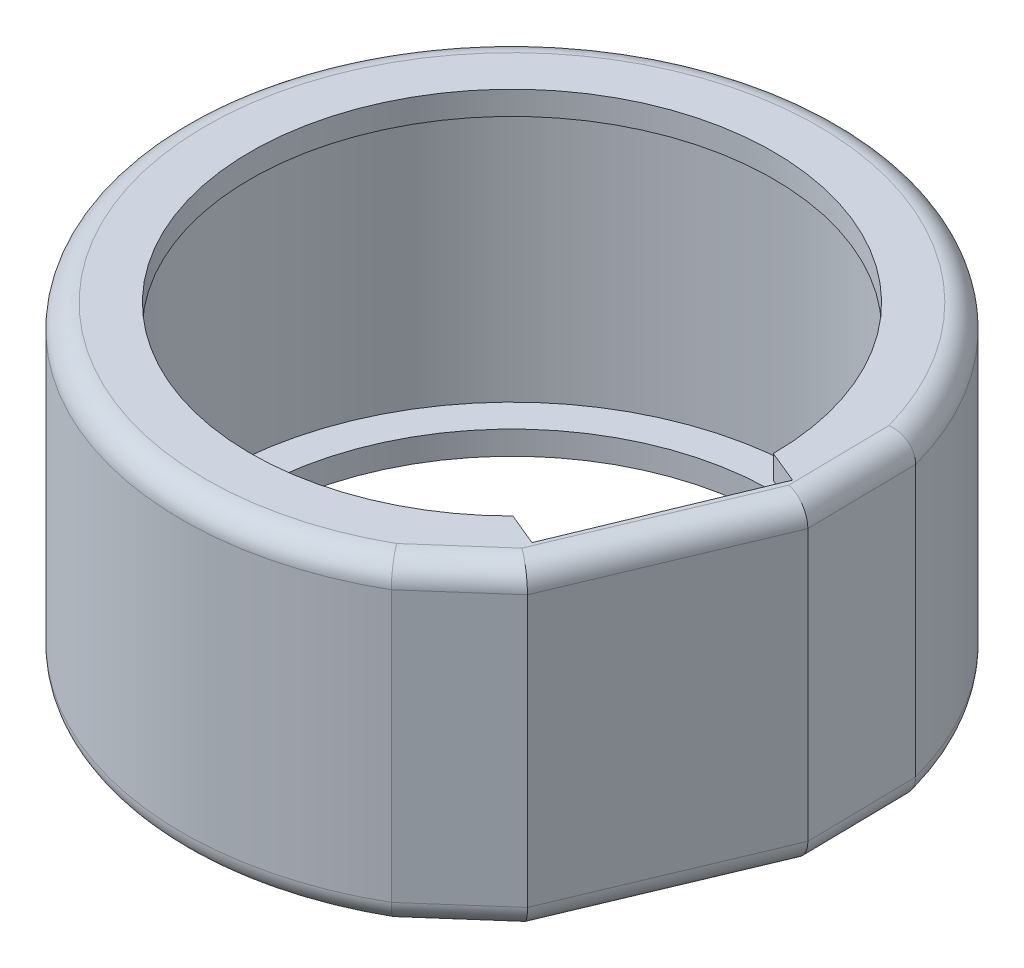
SolidWorks part; units mm, degrees
ref_plane "前视基准面" through (0, 0, 0) normal (0, 0, 1) x (1, 0, 0)
ref_plane "上视基准面" through (0, 0, 0) normal (0, 1, 0) x (1, 0, 0)
ref_plane "右视基准面" through (0, 0, 0) normal (1, 0, 0) x (0, 0, -1)
sketch "草图1" plane through (0, 0, 0) normal (0, 1, 0) x (1, 0, 0)
  line L0 (0, 0) -> (11.1, 0) construction
  line L1 (0, 0) -> (7.8676, -7.8301) construction
  line L6 (0, 0) -> (13.523, 3.6235) construction
  line L7 (0, 0) -> (7, -12.1244) construction
  line L10 (11.1, 0) -> (13.5957, -1.0303) construction
  line L20 (13.5957, -1.0303) -> (10.076, -9.4184)
  line L21 (13.5957, -1.0303) -> (13.523, 3.6235)
  line L22 (10.076, -9.4184) -> (7, -12.1244)
  line L23 (11.1, 0) -> (7.8676, -7.8301)
  arc A0 (11.1, 0) -> (7.8676, -7.8301) centre (0, 0) ccw
  arc A3 (13.523, 3.6235) -> (7, -12.1244) centre (0, 0) ccw
  dimension "D1" = 2.7
  dimension "D2" = 14
  dimension "D3" = 11.1
extrude "凸台-拉伸1" add sketch "草图1" along normal blind 1
sketch "草图2" plane through (0, 0, 0) normal (0, -1, 0) x (-1, 0, 0)
  line L5 (0, 0) -> (-7, -12.1244) construction
  line L7 (0, 0) -> (-13.523, 3.6235) construction
  line L9 (-9.2267, -8.4332) -> (-12.4874, -0.5611)
  line L17 (-13.5957, -1.0303) -> (-13.523, 3.6235)
  line L19 (-13.5957, -1.0303) -> (-10.076, -9.4184)
  line L20 (-10.076, -9.4184) -> (-7, -12.1244)
  arc A0 (-7, -12.1244) -> (-13.523, 3.6235) centre (0, 0) ccw
  arc A1 (-9.2267, -8.4332) -> (-12.4874, -0.5611) centre (0, 0) ccw
  dimension "D1" = 12.5
  dimension "D2" = 14
extrude "凸台-拉伸3" add sketch "草图2" along normal blind 11.5
sketch "草图5" plane through (0, -11.5, 0) normal (0, -1, 0) x (-1, 0, 0)
  line L4 (0, 0) -> (-7, -12.1244) construction
  line L5 (0, 0) -> (-13.523, 3.6235) construction
  line L17 (-13.523, 3.6235) -> (-13.5957, -1.0303)
  line L19 (-10.076, -9.4184) -> (-7, -12.1244)
  line L21 (-11.1, 0) -> (-7.8676, -7.8301) construction
  line L22 (-11.1, 0) -> (-7.8676, -7.8301)
  line L23 (-13.5957, -1.0303) -> (-10.076, -9.4184)
  arc A1 (-7, -12.1244) -> (-13.523, 3.6235) centre (0, 0) ccw
  arc A2 (-7.8676, -7.8301) -> (-11.1, 0) centre (0, 0) ccw construction
  arc A3 (-7.8676, -7.8301) -> (-11.1, 0) centre (0, 0) ccw
extrude "凸台-拉伸4" add sketch "草图5" along normal blind 1
fillet "圆角1" radius 1 4 edges at (13.5593, -12.5, -1.2966) (-12.9343, -12.5, -5.3576) (8.538, -12.5, 10.7714) (11.8358, -12.5, 5.2243) type face fillet first side face at (13.5593, -5.75, -1.2966) first side face at (11.8358, -5.75, 5.2243) first side face at (8.538, -5.75, 10.7714) first side face at (-1.3364, -5.75, -0.5536) second side face at (5.2497, -12.5, 2.3354)
fillet "圆角2" radius 1 4 edges at (13.5593, 1, -1.2966) (-12.9343, 1, -5.3576) (8.538, 1, 10.7714) (11.8358, 1, 5.2243) type face fillet first side face at (13.5593, -5.25, -1.2966) first side face at (11.8358, -5.25, 5.2243) first side face at (8.538, -5.25, 10.7714) first side face at (-1.3364, -5.25, -0.5536) second side face at (-0.3882, 1, -0.1602)
sketch "草图7" plane through (9.4838, 0, 3.9151) normal (-0.9243, 0, -0.3816) x (-0.3816, 0, 0.9243)
  line L4 (-4.2355, 1) -> (-4.2355, 0) construction
  line L5 (-4.2355, 1) -> (-4.2355, 0)
  line L6 (-4.2355, 1) -> (4.2355, 1) construction
  line L7 (-4.2355, 1) -> (4.2355, 1)
  line L9 (-4.2355, 0) -> (4.2355, 0)
  line L10 (-4.2355, 0) -> (-4.2355, 1)
  line L11 (-4.2355, 1) -> (4.2355, 1)
  line L12 (4.2355, 0) -> (4.2355, 1)
extrude "切除-拉伸1" cut sketch "草图7" against normal blind 1.5 contours L9 L12 L7 L5
sketch3d "3DSketch1"
  spline S0 degree 1 poles (-13.1347, 1999.9934, 4.8456) (-13.1347, -2011.4808, 4.8456) knots -173.912465 -173.912465 174.91137 174.91137 only from (-13.1347, 0, 4.8456) to (-13.1347, -11.5, 4.8456) construction
  spline S1 degree 1 poles (-13.1347, 0, 4.8456) (-13.1347, -11.5, 4.8456) knots 0 0 1 1
sketch3d "3DSketch2"
  spline S0 degree 3 poles (7, -5.75, 12.1244) (-6.9766, -5.75, 20.1937) (-19.1104, -5.75, 9.5527) (-12.9343, -5.75, -5.3576) (-6.7583, -5.75, -20.2678) (9.3459, -5.75, -19.2123) (13.523, -5.75, -3.6235) knots 0 0 0 0 0.5 0.5 0.5 1 1 1 1 weights 1 0.547626 0.547626 1 0.547626 0.547626 1 construction
  spline S1 degree 3 poles (7, -5.75, 12.1244) (-6.9766, -5.75, 20.1937) (-19.1104, -5.75, 9.5527) (-12.9343, -5.75, -5.3576) (-6.7583, -5.75, -20.2678) (9.3459, -5.75, -19.2123) (13.523, -5.75, -3.6235) knots 0 0 0 0 0.5 0.5 0.5 1 1 1 1 weights 1 0.547626 0.547626 1 0.547626 0.547626 1
ref_plane "Plane1" through (-13.1347, 0, 4.8456) normal (-0.9382, 0, 0.3461) x (0.3461, 0, 0.9382)
sketch "Sketch2" plane through (-13.1347, 0, 4.8456) normal (-0.9382, 0, 0.3461) x (0.3461, 0, 0.9382)
  line L0 (0, 0) -> (0, -11.5) construction
  circle A0 centre (0, -5.75) radius 0.8
  point P0 (0, -5.75)
extrude "Cut-Extrude1" cut sketch "Sketch2" against normal blind 10
